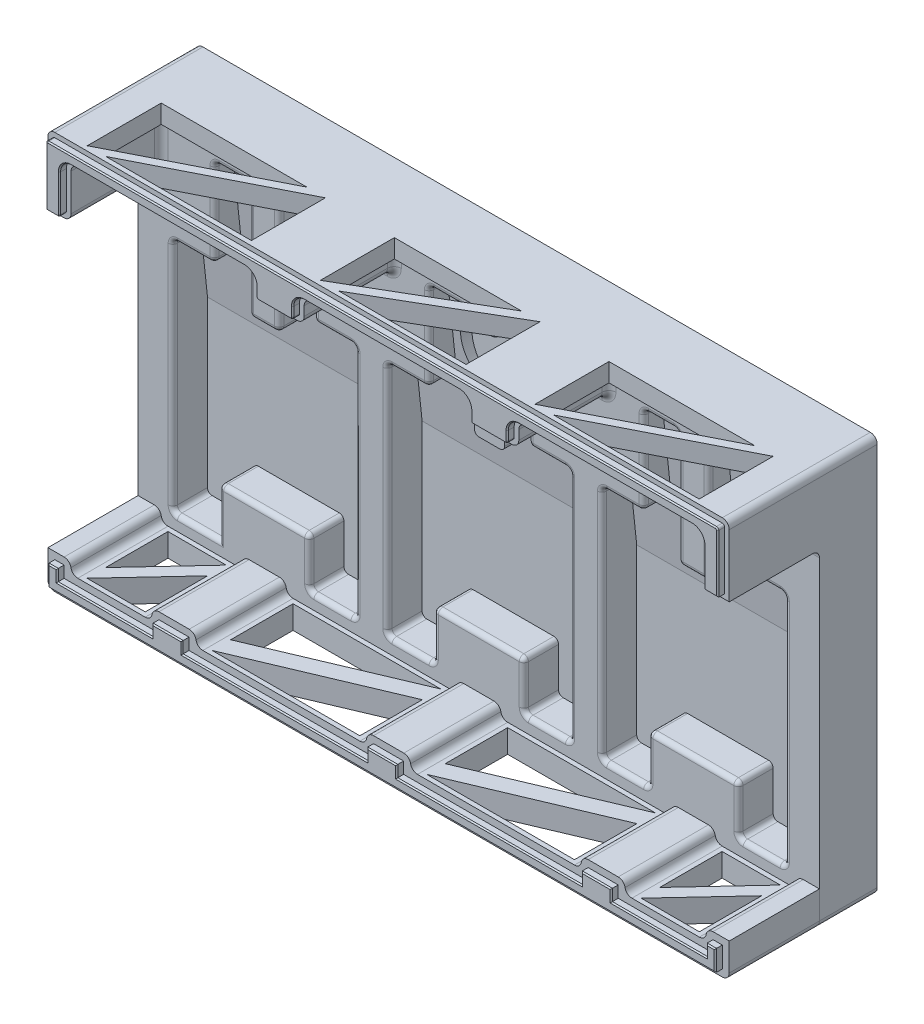
SolidWorks part; units mm, degrees
material "PP generico"
ref_plane "Piano frontale" through (0, 0, 0) normal (0, 0, 1) x (1, 0, 0)
ref_plane "Piano superiore" through (0, 0, 0) normal (0, 1, 0) x (1, 0, 0)
ref_plane "Piano destro" through (0, 0, 0) normal (1, 0, 0) x (0, 0, -1)
sketch "Schizzo1" plane through (0, 0, 0) normal (0, 0, 1) x (1, 0, 0)
  line L1 (-147.3, 86) -> (147.3, 86)
  line L2 (-147.3, 86) -> (-147.3, -86)
  line L3 (-147.3, -86) -> (147.3, -86)
  line L4 (147.3, 86) -> (147.3, -86)
  dimension "D1" = 294.6
  dimension "D2" = 172
  dimension "D3" = 147.3
  dimension "D4" = 86
extrude "Estrusione-Estrusione1" add sketch "Schizzo1" along normal blind 10 contours L1 L4 L3 L2
sketch "Schizzo2" plane through (0, 0, 10) normal (0, 0, 1) x (1, 0, 0)
  line L0 (-73.3, -70) -> (-53.3, -70)
  line L1 (-147.3, 86) -> (147.3, 86)
  line L2 (-147.3, 86) -> (-147.3, -86)
  line L3 (-6.3232, -86) -> (147.3, -86)
  line L4 (147.3, 86) -> (147.3, -86)
  line L9 (-114.3, 70) -> (-99.3, 70)
  line L10 (-132.3, 32) -> (-132.3, -70)
  line L11 (-132.3, -70) -> (-112.3, -70)
  line L12 (-53.3, 32) -> (-53.3, -70)
  line L14 (-39.5, 32) -> (-39.5, -69.8088)
  line L15 (-39.5, -69.8088) -> (-19.5, -69.8088)
  line L16 (39.5, 32) -> (39.5, -69.8088)
  line L18 (53.3, 32) -> (53.3, -69.8088)
  line L19 (53.3, -69.8088) -> (73.3, -69.8088)
  line L20 (132.3, 32) -> (132.3, -69.8088)
  line L21 (-112.3, -49) -> (-73.3, -49)
  line L22 (-112.3, -49) -> (-112.3, -70)
  line L24 (-73.3, -49) -> (-73.3, -70)
  line L25 (19.5, -69.8088) -> (39.5, -69.8088)
  line L26 (-19.5, -48.8088) -> (19.5, -48.8088)
  line L27 (-19.5, -48.8088) -> (-19.5, -69.8088)
  line L29 (19.5, -48.8088) -> (19.5, -69.8088)
  line L30 (73.3, -48.8088) -> (112.3, -48.8088)
  line L31 (73.3, -48.8088) -> (73.3, -69.8088)
  line L33 (112.3, -48.8088) -> (112.3, -69.8088)
  line L34 (112.3, -69.8088) -> (132.3, -69.8088)
  line L35 (-86.3, 70) -> (-71.3, 70)
  line L38 (-132.3, 32) -> (-114.3, 32)
  line L39 (-114.3, 70) -> (-114.3, 32)
  line L42 (-53.3, 32) -> (-71.3, 32)
  line L43 (-71.3, 70) -> (-71.3, 32)
  line L45 (-99.3, 70) -> (-99.3, 20)
  line L46 (-99.3, 20) -> (-86.3, 20)
  line L47 (-86.3, 70) -> (-86.3, 20)
  line L48 (-21.5, 70) -> (-21.5, 32)
  line L49 (-39.5, 32) -> (-21.5, 32)
  line L50 (-21.5, 70) -> (-6.5, 70)
  line L51 (-6.5, 70) -> (-6.5, 20)
  line L52 (6.5, 70) -> (6.5, 20)
  line L53 (6.5, 70) -> (21.5, 70)
  line L54 (21.5, 70) -> (21.5, 32)
  line L55 (39.5, 32) -> (21.5, 32)
  line L56 (-6.5, 20) -> (6.5, 20)
  line L57 (71.3, 70) -> (71.3, 32)
  line L58 (53.3, 32) -> (71.3, 32)
  line L59 (71.3, 70) -> (86.3, 70)
  line L60 (86.3, 70) -> (86.3, 20)
  line L61 (99.3, 70) -> (99.3, 20)
  line L62 (99.3, 70) -> (114.3, 70)
  line L63 (114.3, 70) -> (114.3, 32)
  line L64 (132.3, 32) -> (114.3, 32)
  line L65 (86.3, 20) -> (99.3, 20)
  line M19 (-147.3, 86) -> (-147.3, -86)
  line M20 (-147.3, -86) -> (147.3, -86)
  line M21 (147.3, -86) -> (147.3, 86)
  line M22 (147.3, 86) -> (-147.3, 86)
  dimension "D3" = 15
  dimension "D4" = 13.8
  dimension "D5" = 140
  dimension "D6" = 38
  dimension "D7" = 38
  dimension "D8" = 20
  dimension "D9" = 20
  dimension "D10" = 21
  dimension "D11" = 20
  dimension "D12" = 20
  dimension "D13" = 16
  dimension "D14" = 0
  dimension "D16" = 20
  dimension "D17" = 20
  dimension "D18" = 21
  dimension "D19" = 21
  dimension "D20" = 18
  dimension "D21" = 18
  dimension "D22" = 15
  dimension "D23" = 15
  dimension "D24" = 50
  dimension "D25" = 3
extrude "Estrusione-Estrusione2" add sketch "Schizzo2" along normal blind 15 contours L34 L33 L30 L31 L19 L18 L20 L29 L26 L27 L15 L14 L16 L25 L24 L21 L22 L11 L10 L9 L12 L0 M22 M19 M20 M21 region at (0, 82.5886, 10)
sketch "Schizzo4" plane through (132.3, 0, 0) normal (-1, 0, 0) x (0, 0, 1)
  line L0 (10, 70) -> (10, 3.34)
  line L1 (10, 32) -> (10, -69.8088) construction
  line L2 (10, 3.34) -> (17.12, 70)
  line L4 (17.12, 70) -> (10, 70)
  dimension "D3" = 73.1488
extrude "Estrusione-Estrusione3" add sketch "Schizzo4" along normal up to surface (264.6 mm away) up to face at (-132.3, -19, 17.5)
sketch "Schizzo5" plane through (0, 0, 25) normal (0, 0, 1) x (1, 0, 0)
  line L0 (-147.3, 86) -> (-147.3, 56)
  line L1 (-147.3, 86) -> (-147.3, -86) construction
  line L2 (-147.3, 56) -> (-137.3, 56)
  line L3 (-137.3, 56) -> (-137.3, 78)
  line L4 (-137.3, 78) -> (-56.3, 78)
  line L5 (-56.3, 78) -> (-56.3, 68)
  line L6 (-56.3, 68) -> (-36.5, 68)
  line L7 (-36.5, 68) -> (-36.5, 78)
  line L8 (-36.5, 78) -> (36.5, 78)
  line L9 (36.5, 78) -> (36.5, 68)
  line L10 (36.5, 68) -> (56.3, 68)
  line L11 (56.3, 68) -> (56.3, 78)
  line L12 (56.3, 78) -> (137.3, 78)
  line L13 (137.3, 78) -> (137.3, 56)
  line L14 (137.3, 56) -> (147.3, 56)
  line L15 (147.3, -86) -> (147.3, 86) construction
  line L16 (147.3, 56) -> (147.3, 86)
  line L17 (147.3, 86) -> (-147.3, 86)
  line L18 (-21.5, 70) -> (-21.5, 32) construction
  line L19 (-71.3, 32) -> (-71.3, 70) construction
  line L20 (21.5, 32) -> (21.5, 70) construction
  line L22 (71.3, 70) -> (71.3, 32) construction
  dimension "D1" = 30
  dimension "D2" = 30
  dimension "D3" = 10
  dimension "D4" = 10
  dimension "D5" = 15
  dimension "D6" = 15
  dimension "D7" = 8
  dimension "D8" = 15
  dimension "D9" = 8
  dimension "D10" = 15
  dimension "D11" = 8
extrude "Estrusione-Estrusione4" add sketch "Schizzo5" along normal blind 39
fillet "Raccordo1" radius 3 27 edges at (137.3, 67, 25) (36.5, 73, 25) (56.3, 73, 25) (-36.5, 73, 25) (-56.3, 73, 25) (147.3, 86, 32) (137.3, 78, 44.5) (137.3, 56, 44.5) (142.3, 56, 25) (96.8, 78, 25) (56.3, 78, 44.5) (36.5, 78, 44.5) (36.5, 68, 44.5) (56.3, 68, 44.5) (46.4, 68, 25) (0, 78, 25) (-36.5, 68, 44.5) (-36.5, 78, 44.5) (-46.4, 68, 25) (-56.3, 68, 44.5) (-147.3, 86, 32) (-137.3, 56, 44.5) (-137.3, 78, 44.5) (-96.8, 78, 25) (-142.3, 56, 25) (-137.3, 67, 25) (-56.3, 78, 44.5)
fillet "Raccordo2" radius 2 31 edges at (-114.3, 51, 25) (-123.3, 32, 25) (-53.3, -70, 17.5) (-132.3, -70, 17.5) (-112.3, -49, 17.5) (-73.3, -70, 17.5) (-73.3, -49, 17.5) (-53.3, 32, 19.0306) (-99.3, 70, 21.06) (-86.3, 70, 21.06) (-71.3, 70, 21.06) (-71.3, 32, 19.0306) (-86.3, 20, 18.3897) (-99.3, 20, 18.3897) (-71.3, 51, 25) (-86.3, 45, 25) (-99.3, 45, 25) (-92.8, 20, 25) (-106.8, 70, 25) (-78.8, 70, 25) (-62.3, 32, 25) (-53.3, -19, 25) (-63.3, -70, 25) (-73.3, -59.5, 25) (-92.8, -49, 25) (-112.3, -59.5, 25) (-122.3, -70, 25) (-132.3, -19, 25) (-114.3, 70, 21.06) (-132.3, 32, 19.0306) (-114.3, 32, 19.0306)
fillet "Raccordo4" radius 2 64 edges at (114.3, 51, 25) (106.8, 70, 25) (78.8, 70, 25) (53.3, -18.9044, 25) (132.3, -69.8088, 17.5) (132.3, 32, 19.0306) (86.3, 20, 18.3897) (114.3, 32, 19.0306) (114.3, 70, 21.06) (99.3, 70, 21.06) (86.3, 70, 21.06) (71.3, 51, 25) (71.3, 70, 21.06) (53.3, 32, 19.0306) (73.3, -69.8088, 17.5) (73.3, -48.8088, 17.5) (112.3, -69.8088, 17.5) (132.3, -18.9044, 25) (123.3, 32, 25) (99.3, 45, 25) (86.3, 45, 25) (92.8, 20, 25) (62.3, 32, 25) (92.8, -48.8088, 25) (63.3, -69.8088, 25) (73.3, -59.3088, 25) (112.3, -59.3088, 25) (122.3, -69.8088, 25) (112.3, -48.8088, 17.5) (99.3, 20, 18.3897) (71.3, 32, 19.0306) (53.3, -69.8088, 17.5) (-39.5, -69.8088, 17.5) (19.5, -69.8088, 17.5) (39.5, -69.8088, 17.5) (19.5, -48.8088, 17.5) (-19.5, -48.8088, 17.5) (-19.5, -69.8088, 17.5) (-39.5, 32, 19.0306) (-21.5, 70, 21.06) (6.5, 70, 21.06) (21.5, 70, 21.06) (39.5, 32, 19.0306) (-21.5, 32, 19.0306) (-6.5, 20, 18.3897) (6.5, 20, 18.3897) (21.5, 32, 19.0306) (30.5, 32, 25) (21.5, 51, 25) (6.5, 45, 25) (-21.5, 51, 25) (-30.5, 32, 25) (-6.5, 45, 25) (0, 20, 25) (39.5, -18.9044, 25) (29.5, -69.8088, 25) (19.5, -59.3088, 25) (0, -48.8088, 25) (-19.5, -59.3088, 25) (-39.5, -18.9044, 25) (-29.5, -69.8088, 25) (-14, 70, 25) (14, 70, 25) (-6.5, 70, 21.06)
sketch "Schizzo8" plane through (0, 0, 25) normal (0, 0, 1) x (1, 0, 0)
  line L0 (-147.3, -86) -> (-147.3, -71)
  line L1 (-147.3, 53) -> (-147.3, -86) construction
  line L2 (-147.3, -71) -> (-137.3, -71)
  line L3 (-137.3, -71) -> (-137.3, -76)
  line L4 (-137.3, -76) -> (-102.3, -76)
  line L5 (-102.3, -76) -> (-102.3, -71)
  line L6 (-102.3, -71) -> (-83.3, -71)
  line L7 (-83.3, -71) -> (-83.3, -76)
  line L8 (-83.3, -76) -> (-9.5, -76)
  line L9 (-9.5, -76) -> (-9.5, -71)
  line L10 (-9.5, -71) -> (9.5, -71)
  line L11 (9.5, -71) -> (9.5, -76)
  line L12 (9.5, -76) -> (83.3, -76)
  line L13 (83.3, -76) -> (83.3, -71)
  line L14 (83.3, -71) -> (102.3, -71)
  line L15 (102.3, -71) -> (102.3, -76)
  line L16 (102.3, -76) -> (137.3, -76)
  line L17 (137.3, -76) -> (137.3, -71)
  line L18 (137.3, -71) -> (147.3, -71)
  line L19 (147.3, -86) -> (147.3, 53) construction
  line L20 (147.3, -71) -> (147.3, -86)
  line L21 (147.3, -86) -> (-147.3, -86)
  line L22 (-110.3, -51) -> (-110.3, -72) construction
  line L23 (-75.3, -68) -> (-75.3, -51) construction
  line L26 (75.3, -50.8088) -> (75.3, -67.8088) construction
  line L27 (110.3, -67.8088) -> (110.3, -50.8088) construction
  line L28 (-17.5, -50.8088) -> (-17.5, -67.8088) construction
  line L29 (17.5, -67.8088) -> (17.5, -50.8088) construction
  dimension "D1" = 10
  dimension "D2" = 10
  dimension "D3" = 15
  dimension "D4" = 15
  dimension "D5" = 15
  dimension "D6" = 15
  dimension "D7" = 15
  dimension "D8" = 8
  dimension "D9" = 8
  dimension "D10" = 8
  dimension "D11" = 8
  dimension "D12" = 8
  dimension "D13" = 8
  dimension "D14" = 10
  dimension "D15" = 10
  dimension "D16" = 10
  dimension "D17" = 10
extrude "Estrusione-Estrusione5" add sketch "Schizzo8" along normal up to surface (39 mm away) up to face at (0, 71.8414, 64)
fillet "Raccordo8" radius 3 2 edges at (147.3, -86, 12.5) (-147.3, -86, 12.5)
sketch "Schizzo10" plane through (0, 0, 64) normal (0, 0, 1) x (1, 0, 0)
  line L16 (-38.5, 71) -> (-38.5, 75)
  line L17 (-38.5, 71) -> (-38.5, 75)
  line L18 (140.3, -74) -> (140.3, -79)
  line L19 (140.3, -74) -> (140.3, -79)
  line L20 (99.3, -79) -> (99.3, -74)
  line L21 (99.3, -79) -> (99.3, -74)
  line L22 (86.3, -74) -> (86.3, -79)
  line L23 (86.3, -74) -> (86.3, -79)
  line L24 (6.5, -79) -> (6.5, -74)
  line L25 (6.5, -79) -> (6.5, -74)
  line L26 (-6.5, -74) -> (-6.5, -79)
  line L27 (-6.5, -74) -> (-6.5, -79)
  line L28 (-86.3, -79) -> (-86.3, -74)
  line L29 (-86.3, -79) -> (-86.3, -74)
  line L30 (38.5, 75) -> (38.5, 71)
  line L31 (38.5, 75) -> (38.5, 71)
  line L32 (-99.3, -74) -> (-99.3, -79)
  line L33 (-99.3, -74) -> (-99.3, -79)
  line L34 (-140.3, -79) -> (-140.3, -74)
  line L35 (-140.3, -79) -> (-140.3, -74)
  line L72 (-144.3, -83) -> (144.3, -83)
  line L73 (144.3, -83) -> (144.3, -74)
  line L74 (144.3, -74) -> (140.3, -74)
  line L75 (140.3, -79) -> (99.3, -79)
  line L76 (99.3, -74) -> (86.3, -74)
  line L77 (86.3, -79) -> (6.5, -79)
  line L78 (6.5, -74) -> (-6.5, -74)
  line L79 (-6.5, -79) -> (-86.3, -79)
  line L80 (-86.3, -74) -> (-99.3, -74)
  line L81 (-99.3, -79) -> (-140.3, -79)
  line L82 (-140.3, -74) -> (-144.3, -74)
  line L83 (-144.3, -74) -> (-144.3, -83)
  line L84 (-144.3, -83) -> (144.3, -83)
  line L85 (144.3, -83) -> (144.3, -74)
  line L86 (144.3, -74) -> (140.3, -74)
  line L87 (140.3, -79) -> (99.3, -79)
  line L88 (99.3, -74) -> (86.3, -74)
  line L89 (86.3, -79) -> (6.5, -79)
  line L90 (6.5, -74) -> (-6.5, -74)
  line L91 (-6.5, -79) -> (-86.3, -79)
  line L92 (-86.3, -74) -> (-99.3, -74)
  line L93 (-99.3, -79) -> (-140.3, -79)
  line L94 (-140.3, -74) -> (-144.3, -74)
  line L95 (-144.3, -74) -> (-144.3, -83)
  line L100 (140.3, 58) -> (145.3, 58)
  line L101 (145.3, 58) -> (145.3, 83)
  line L102 (144.3, 84) -> (-144.3, 84)
  line L103 (-145.3, 83) -> (-145.3, 58)
  line L104 (-145.3, 58) -> (-140.3, 58)
  line L105 (-139.3, 59) -> (-139.3, 75)
  line L106 (-134.3, 80) -> (-59.3, 80)
  line L107 (-54.3, 75) -> (-54.3, 71)
  line L108 (-53.3, 70) -> (-39.5, 70)
  line L110 (-33.5, 80) -> (33.5, 80)
  line L112 (39.5, 70) -> (53.3, 70)
  line L113 (54.3, 71) -> (54.3, 75)
  line L114 (59.3, 80) -> (134.3, 80)
  line L115 (139.3, 75) -> (139.3, 59)
  line L116 (140.3, 58) -> (145.3, 58)
  line L117 (145.3, 58) -> (145.3, 83)
  line L118 (144.3, 84) -> (-144.3, 84)
  line L119 (-145.3, 83) -> (-145.3, 58)
  line L120 (-145.3, 58) -> (-140.3, 58)
  line L121 (-139.3, 59) -> (-139.3, 75)
  line L122 (-134.3, 80) -> (-59.3, 80)
  line L123 (-54.3, 75) -> (-54.3, 71)
  line L124 (-53.3, 70) -> (-39.5, 70)
  line L126 (-33.5, 80) -> (33.5, 80)
  line L128 (39.5, 70) -> (53.3, 70)
  line L129 (54.3, 71) -> (54.3, 75)
  line L130 (59.3, 80) -> (134.3, 80)
  line L131 (139.3, 75) -> (139.3, 59)
  arc A85 (145.3, 83) -> (144.3, 84) centre (144.3, 83) ccw
  arc A86 (-144.3, 84) -> (-145.3, 83) centre (-144.3, 83) ccw
  arc A104 (-140.3, 58) -> (-139.3, 59) centre (-140.3, 59) ccw
  arc A105 (-134.3, 80) -> (-139.3, 75) centre (-134.3, 75) ccw
  arc A106 (-54.3, 75) -> (-59.3, 80) centre (-59.3, 75) ccw
  arc A107 (-54.3, 71) -> (-53.3, 70) centre (-53.3, 71) ccw
  arc A108 (-39.5, 70) -> (-38.5, 71) centre (-39.5, 71) ccw
  arc A109 (-33.5, 80) -> (-38.5, 75) centre (-33.5, 75) ccw
  arc A110 (38.5, 75) -> (33.5, 80) centre (33.5, 75) ccw
  arc A111 (38.5, 71) -> (39.5, 70) centre (39.5, 71) ccw
  arc A112 (53.3, 70) -> (54.3, 71) centre (53.3, 71) ccw
  arc A113 (59.3, 80) -> (54.3, 75) centre (59.3, 75) ccw
  arc A114 (139.3, 75) -> (134.3, 80) centre (134.3, 75) ccw
  arc A115 (139.3, 59) -> (140.3, 58) centre (140.3, 59) ccw
  arc A117 (145.3, 83) -> (144.3, 84) centre (144.3, 83) ccw
  arc A118 (-144.3, 84) -> (-145.3, 83) centre (-144.3, 83) ccw
  arc A120 (-140.3, 58) -> (-139.3, 59) centre (-140.3, 59) ccw
  arc A121 (-134.3, 80) -> (-139.3, 75) centre (-134.3, 75) ccw
  arc A122 (-54.3, 75) -> (-59.3, 80) centre (-59.3, 75) ccw
  arc A123 (-54.3, 71) -> (-53.3, 70) centre (-53.3, 71) ccw
  arc A124 (-39.5, 70) -> (-38.5, 71) centre (-39.5, 71) ccw
  arc A125 (-33.5, 80) -> (-38.5, 75) centre (-33.5, 75) ccw
  arc A126 (38.5, 75) -> (33.5, 80) centre (33.5, 75) ccw
  arc A127 (38.5, 71) -> (39.5, 70) centre (39.5, 71) ccw
  arc A128 (53.3, 70) -> (54.3, 71) centre (53.3, 71) ccw
  arc A129 (59.3, 80) -> (54.3, 75) centre (59.3, 75) ccw
  arc A130 (139.3, 75) -> (134.3, 80) centre (134.3, 75) ccw
  arc A131 (139.3, 59) -> (140.3, 58) centre (140.3, 59) ccw
  dimension "D1" = 2
  dimension "D2" = 3
extrude "Estrusione-Estrusione6" add sketch "Schizzo10" along normal blind 3
sketch "Schizzo11" plane through (0, 0, 0) normal (0, 0, 1) x (1, 0, 0)
  line L84 (-144.3, -83) -> (144.3, -83)
  line L85 (144.3, -83) -> (144.3, -74)
  line L86 (144.3, -74) -> (140.3, -74)
  line L87 (134.3839, -79) -> (107.2161, -79)
  line L88 (101.3, -74) -> (84.3, -74)
  line L89 (78.3839, -79) -> (14.4161, -79)
  line L90 (8.5, -74) -> (-8.5, -74)
  line L91 (-14.4161, -79) -> (-78.3839, -79)
  line L92 (-84.3, -74) -> (-101.3, -74)
  line L93 (-107.2161, -79) -> (-134.3839, -79)
  line L94 (-140.3, -74) -> (-144.3, -74)
  line L95 (-144.3, -74) -> (-144.3, -83)
  line L116 (140.3, 58) -> (144.3, 58)
  line L117 (145.3, 59) -> (145.3, 83)
  line L118 (144.3, 84) -> (-144.3, 84)
  line L119 (-145.3, 83) -> (-145.3, 59)
  line L120 (-144.3, 58) -> (-140.3, 58)
  line L121 (-139.3, 59) -> (-139.3, 75)
  line L122 (-134.3, 80) -> (-59.3, 80)
  line L123 (-54.3, 75) -> (-54.3, 71)
  line L124 (-53.3, 70) -> (-39.5, 70)
  line L125 (-38.5, 71) -> (-38.5, 75)
  line L126 (-33.5, 80) -> (33.5, 80)
  line L127 (38.5, 75) -> (38.5, 71)
  line L128 (39.5, 70) -> (53.3, 70)
  line L129 (54.3, 71) -> (54.3, 75)
  line L130 (59.3, 80) -> (134.3, 80)
  line L131 (139.3, 75) -> (139.3, 59)
  arc A96 (134.3839, -79) -> (140.3, -74) centre (134.3839, -73) ccw
  arc A97 (101.3, -74) -> (107.2161, -79) centre (107.2161, -73) ccw
  arc A98 (78.3839, -79) -> (84.3, -74) centre (78.3839, -73) ccw
  arc A99 (8.5, -74) -> (14.4161, -79) centre (14.4161, -73) ccw
  arc A100 (-14.4161, -79) -> (-8.5, -74) centre (-14.4161, -73) ccw
  arc A101 (-84.3, -74) -> (-78.3839, -79) centre (-78.3839, -73) ccw
  arc A102 (-107.2161, -79) -> (-101.3, -74) centre (-107.2161, -73) ccw
  arc A103 (-140.3, -74) -> (-134.3839, -79) centre (-134.3839, -73) ccw
  arc A116 (144.3, 58) -> (145.3, 59) centre (144.3, 59) ccw
  arc A117 (145.3, 83) -> (144.3, 84) centre (144.3, 83) ccw
  arc A118 (-144.3, 84) -> (-145.3, 83) centre (-144.3, 83) ccw
  arc A119 (-145.3, 59) -> (-144.3, 58) centre (-144.3, 59) ccw
  arc A120 (-140.3, 58) -> (-139.3, 59) centre (-140.3, 59) ccw
  arc A121 (-134.3, 80) -> (-139.3, 75) centre (-134.3, 75) ccw
  arc A122 (-54.3, 75) -> (-59.3, 80) centre (-59.3, 75) ccw
  arc A123 (-54.3, 71) -> (-53.3, 70) centre (-53.3, 71) ccw
  arc A124 (-39.5, 70) -> (-38.5, 71) centre (-39.5, 71) ccw
  arc A125 (-33.5, 80) -> (-38.5, 75) centre (-33.5, 75) ccw
  arc A126 (38.5, 75) -> (33.5, 80) centre (33.5, 75) ccw
  arc A127 (38.5, 71) -> (39.5, 70) centre (39.5, 71) ccw
  arc A128 (53.3, 70) -> (54.3, 71) centre (53.3, 71) ccw
  arc A129 (59.3, 80) -> (54.3, 75) centre (59.3, 75) ccw
  arc A130 (139.3, 75) -> (134.3, 80) centre (134.3, 75) ccw
  arc A131 (139.3, 59) -> (140.3, 58) centre (140.3, 59) ccw
extrude "Taglio-Estrusione1" cut sketch "Schizzo11" along normal blind 4
fillet "Raccordo9" radius 3 4 edges at (9.5, -76, 44.5) (-83.3, -76, 44.5) (-102.3, -71, 44.5) (-9.5, -71, 44.5)
fillet "Raccordo10" radius 3 4 edges at (-9.5, -76, 44.5) (-137.3, -71, 44.5) (-83.3, -71, 44.5) (-102.3, -76, 44.5)
fillet "Raccordo11" radius 3 2 edges at (-137.3, -76, 44.5) (137.3, -71, 44.5)
fillet "Raccordo12" radius 3 2 edges at (137.3, -76, 44.5) (102.3, -71, 44.5)
fillet "Raccordo13" radius 3 3 edges at (102.3, -76, 44.5) (9.5, -71, 44.5) (83.3, -71, 44.5)
fillet "Raccordo14" radius 3 2 edges at (-147.3, -86, 44.5) (147.3, -86, 44.5)
chamfer "Smusso1" distance 0.5 angle 45 20 edges at (144.3, -78.5, 67) (0, -83, 67) (-144.3, -78.5, 67) (-142.3, -74, 67) (-140.3, -76.5, 67) (-119.8, -79, 67) (-99.3, -76.5, 67) (-92.8, -74, 67) (-86.3, -76.5, 67) (-46.4, -79, 67) (-6.5, -76.5, 67) (0, -74, 67) (6.5, -76.5, 67) (46.4, -79, 67) (86.3, -76.5, 67) (92.8, -74, 67) (99.3, -76.5, 67) (119.8, -79, 67) (140.3, -76.5, 67) (142.3, -74, 67)
chamfer "Smusso2" distance 0.5 angle 45 30 edges at (142.8, 58, 67) (139.5929, 58.2929, 67) (139.3, 67, 67) (137.8355, 78.5355, 67) (96.8, 80, 67) (55.7645, 78.5355, 67) (54.3, 73, 67) (54.0071, 70.2929, 67) (46.4, 70, 67) (38.7929, 70.2929, 67) (38.5, 73, 67) (37.0355, 78.5355, 67) (0, 80, 67) (-37.0355, 78.5355, 67) (-38.5, 73, 67) (-38.7929, 70.2929, 67) (-46.4, 70, 67) (-54.0071, 70.2929, 67) (-54.3, 73, 67) (-55.7645, 78.5355, 67) (-96.8, 80, 67) (-137.8355, 78.5355, 67) (-139.3, 67, 67) (-139.5929, 58.2929, 67) (-142.8, 58, 67) (-145.3, 70.5, 67) (-145.0071, 83.7071, 67) (0, 84, 67) (145.0071, 83.7071, 67) (145.3, 70.5, 67)
sketch "Schizzo12" plane through (0, 78, 0) normal (0, -1, 0) x (1, 0, 0)
  line L0 (-132.3, 30) -> (-132.3, 62)
  line L1 (-132.3, 62) -> (-69.3, 30)
  line L2 (-69.3, 30) -> (-132.3, 30)
  line L3 (-134.3, 64) -> (-134.3, 28) construction
  line L4 (-134.3, 28) -> (-59.3, 28) construction
  line L5 (-124.3, 62) -> (-61.3, 62)
  line L6 (-61.3, 62) -> (-61.3, 30)
  line L7 (-61.3, 30) -> (-124.3, 62)
  line L8 (-134.3, 64) -> (-59.3, 64) construction
  line L9 (-59.3, 28) -> (-59.3, 64) construction
  line L10 (132.3, 62) -> (132.3, 30)
  line L11 (132.3, 30) -> (69.3, 62)
  line L12 (61.3, 62) -> (124.3, 30)
  line L13 (124.3, 30) -> (61.3, 30)
  line L14 (61.3, 30) -> (61.3, 62)
  line L15 (69.3, 62) -> (132.3, 62)
  line L16 (59.3, 64) -> (59.3, 28) construction
  line L17 (-33.5, 28) -> (33.5, 28) construction
  line L18 (-31.5, 30) -> (23.5, 30)
  line L19 (23.5, 30) -> (-31.5, 62)
  line L20 (-31.5, 62) -> (-31.5, 30)
  line L21 (-23.5, 62) -> (31.5, 62)
  line L22 (31.5, 62) -> (31.5, 30)
  line L23 (31.5, 30) -> (-23.5, 62)
  line L24 (-33.5, 64) -> (-33.5, 28) construction
  line L25 (33.5, 28) -> (33.5, 64) construction
  line L27 (-33.5, 64) -> (33.5, 64) construction
  dimension "D1" = 2
  dimension "D2" = 2
  dimension "D3" = 2
  dimension "D4" = 2
  dimension "D5" = 2
  dimension "D6" = 2
  dimension "D7" = 10
  dimension "D8" = 10
  dimension "D10" = 2
  dimension "D11" = 2
  dimension "D12" = 2
  dimension "D13" = 10
  dimension "D14" = 10
  dimension "D15" = 2
  dimension "D16" = 2
  dimension "D9" = 2
extrude "Taglio-Estrusione2" cut sketch "Schizzo12" against normal blind 10
sketch "Schizzo14" plane through (0, -76, 0) normal (0, 1, 0) x (1, 0, 0)
  line L0 (-78.3, -27) -> (-14.4161, -27)
  line L1 (-14.4161, -27) -> (-78.3, -54)
  line L2 (-78.3, -54) -> (-78.3, -27)
  line L3 (-78.3, -62) -> (-14.4161, -35)
  line L4 (-14.4161, -35) -> (-14.4161, -62)
  line L5 (-14.4161, -62) -> (-78.3, -62)
  line L7 (-6.5, -64) -> (-86.3, -64) construction
  line L8 (-12.4161, -25) -> (-80.3, -25) construction
  line L9 (-12.4161, -64) -> (-12.4161, -25) construction
  line L10 (-144.3, -25) -> (144.3, -25) construction
  line L11 (-80.3, -25) -> (-80.3, -64) construction
  line L12 (78.3839, -62) -> (14.5, -62)
  line L13 (78.3839, -35) -> (78.3839, -62)
  line L14 (14.5, -62) -> (78.3839, -35)
  line L15 (78.3839, -27) -> (14.5, -54)
  line L16 (14.5, -54) -> (14.5, -27)
  line L17 (14.5, -27) -> (78.3839, -27)
  line L20 (12.5, -25) -> (12.5, -64) construction
  line L21 (107.2161, -27) -> (132.3839, -27)
  line L22 (132.3839, -27) -> (107.2161, -54)
  line L23 (107.2161, -54) -> (107.2161, -27)
  line L24 (132.3839, -35) -> (132.3839, -62)
  line L25 (132.3839, -62) -> (107.2161, -62)
  line L26 (107.2161, -62) -> (132.3839, -35)
  line L27 (105.2161, -25) -> (105.2161, -64) construction
  line L28 (134.3839, -64) -> (134.3839, -25) construction
  line L29 (134.3839, -64) -> (105.2161, -64) construction
  line L30 (134.3839, -25) -> (105.2161, -25) construction
  line L31 (-132.3839, -27) -> (-107.2161, -27)
  line L32 (-132.3839, -54) -> (-132.3839, -27)
  line L33 (-107.2161, -27) -> (-132.3839, -54)
  line L34 (-132.3839, -62) -> (-107.2161, -35)
  line L35 (-107.2161, -62) -> (-132.3839, -62)
  line L36 (-107.2161, -35) -> (-107.2161, -62)
  line L37 (-134.3839, -25) -> (-134.3839, -64) construction
  dimension "D1" = 2
  dimension "D2" = 2
  dimension "D3" = 2
  dimension "D4" = 10
  dimension "D5" = 2
  dimension "D6" = 2
  dimension "D7" = 2
  dimension "D9" = 2
  dimension "D10" = 2
  dimension "D11" = 2
  dimension "D12" = 2
  dimension "D13" = 10
  dimension "D14" = 10
  dimension "D15" = 2
  dimension "D17" = 2
  dimension "D8" = 2
  dimension "D16" = 2
extrude "Taglio-Estrusione3" cut sketch "Schizzo14" against normal blind 10
fillet "Raccordo15" radius 3 1 edges at (83.3, -76, 44.5)
sketch "Schizzo15" plane through (0, 20, 0) normal (0, -1, 0) x (1, 0, 0)
  line L1 (-8.824, 26.8346) -> (9.6819, 26.8346)
  line L2 (-8.824, 26.8346) -> (-8.824, 20.3575)
  line L3 (-8.824, 20.3575) -> (9.6819, 20.3575)
  line L4 (9.6819, 26.8346) -> (9.6819, 20.3575)
extrude "Taglio-Estrusione4" cut sketch "Schizzo15" against normal blind 37
sketch "Schizzo16" plane through (0, 0, 20.3575) normal (0, 0, 1) x (1, 0, 0)
  line L1 (-4.5, 20) -> (4.5, 20) construction
  line L2 (-6.5, 22) -> (-6.5, 57) construction
  circle A0 centre (-0.5, 48.5) radius 17.5
  dimension "D1" = 35
  dimension "D2" = 28.5
  dimension "D3" = 6
extrude "Taglio-Estrusione5" cut sketch "Schizzo16" against normal up to surface (10.3575 mm away) and the other way blind 37 up to face at (0, -53.1324, 10)
